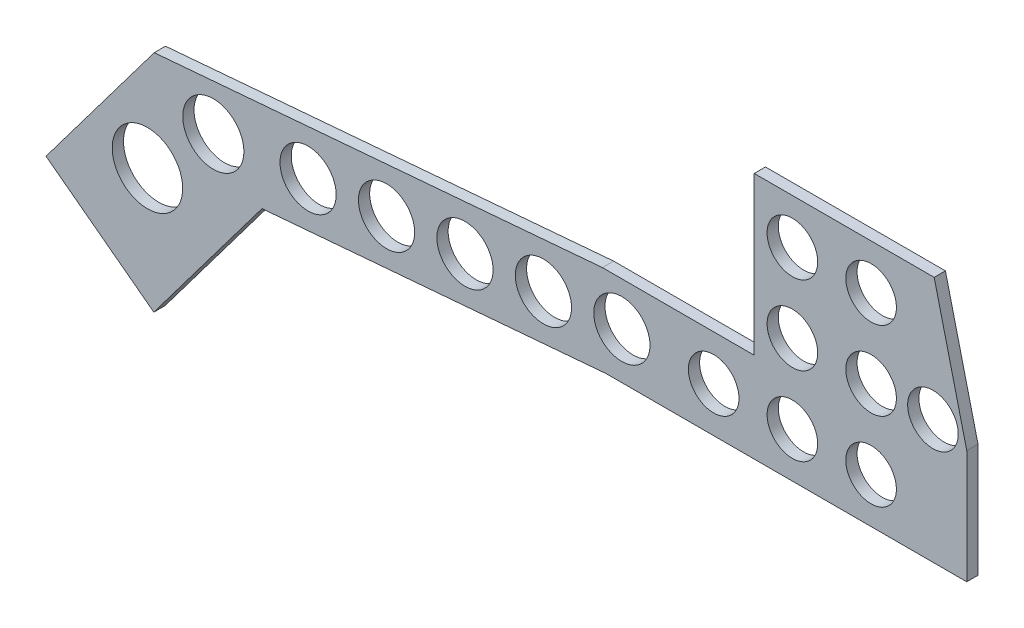
SolidWorks part; units mm, degrees
ref_plane "Front Plane" through (0, 0, 0) normal (0, 0, 1) x (1, 0, 0)
ref_plane "Top Plane" through (0, 0, 0) normal (0, 1, 0) x (1, 0, 0)
ref_plane "Right Plane" through (0, 0, 0) normal (1, 0, 0) x (0, 0, -1)
sketch "Sketch1" plane through (0, 0, 0) normal (0, 0, 1) x (1, 0, 0)
  line L0 (0, 0) -> (50.8, 0)
  line L1 (50.8, 0) -> (60, -37.7541)
  line L2 (60, -37.7541) -> (60, -69.85)
  line L3 (60, -69.85) -> (-41.7879, -69.85)
  line L4 (-41.7879, -69.85) -> (-138.9667, -78.0875)
  line L5 (-138.9667, -78.0875) -> (-169.5142, -118.6768)
  line L6 (-169.5142, -118.6768) -> (-199.9562, -95.7662)
  line L7 (-199.9562, -95.7662) -> (-169.4087, -55.1769)
  line L8 (-169.4087, -55.1769) -> (-42.8625, -44.45)
  line L9 (-42.8625, -44.45) -> (0, -44.45)
  line L10 (0, -44.45) -> (0, 0)
  point P3 (0, 0)
  point P13 (-41.0124, -69.85)
  point P14 (-160.8156, -90.8939)
  point P15 (-131.8845, -85.7557)
  point P16 (-135.633, -86.4159)
  point P17 (-202.104, -88.6533)
  point P18 (-169.6216, -115.7486)
  point P19 (-199.9562, -95.7662)
  dimension "D1" = 50.8
  dimension "D2" = 69.85
  dimension "D3" = 60
  dimension "D4" = 42.8625
  dimension "D5" = 44.45
  dimension "D6" = 38.1
  dimension "D7" = 50.8
  dimension "D8" = 25.4
  dimension "D9" = 50.8
  dimension "D10" = 127
extrude "Boss-Extrude1" add sketch "Sketch1" along normal blind 3.175 contours L7 L8 L9 L10 L0 L1 L2 L3 L4 L5 L6
sketch "Sketch2" plane through (0, 0, 3.175) normal (0, 0, 1) x (1, 0, 0)
  line L0 (-140.6269, -52.7372) -> (-138.4815, -78.0464) construction
  line L1 (-169.4087, -55.1769) -> (-42.8625, -44.45) construction
  line L2 (-41.7879, -69.85) -> (-138.9667, -78.0875) construction
  line L3 (-139.5542, -65.3918) -> (-34.8698, -56.518) construction
  line L4 (-21.4312, -44.45) -> (-21.4313, -69.85) construction
  line L5 (-42.8625, -44.45) -> (0, -44.45) construction
  line L6 (60, -69.85) -> (-41.7879, -69.85) construction
  circle A0 centre (-171.3148, -84.3519) radius 9.9464
  circle A1 centre (-152.715, -66.7142) radius 8.6288
  circle A2 centre (-125.9574, -64.2392) radius 7.9375
  circle A3 centre (-103.8119, -62.362) radius 7.9375
  circle A4 centre (-81.6663, -60.4848) radius 7.9375
  circle A5 centre (-59.5207, -58.6076) radius 7.9375
  circle A6 centre (-37.3751, -56.7304) radius 7.9375
  circle A7 centre (-11.4552, -57.15) radius 7.1438
  circle A8 centre (10.7698, -57.15) radius 7.1438
  circle A9 centre (32.9948, -57.15) radius 7.1437
  circle A10 centre (10.7698, -34.925) radius 7.1438
  circle A11 centre (32.9948, -34.925) radius 7.1437
  circle A12 centre (10.7698, -12.7) radius 7.1438
  circle A13 centre (32.9948, -12.7) radius 7.1437
  circle A14 centre (-11.4552, -34.925) radius 7.1438
  circle A15 centre (-11.4552, -12.7) radius 7.1438
  circle A16 centre (50.4573, -34.925) radius 7.1438
  point P14 (-21.4312, -57.15)
  dimension "D2" = 15.875
  dimension "D3" = 14.2875
  dimension "D6" = 17.4625
  dimension "D1" = 5
  dimension "D4" = 3
  dimension "D5" = 3
extrude "Cut-Extrude1" cut sketch "Sketch2" against normal through all
